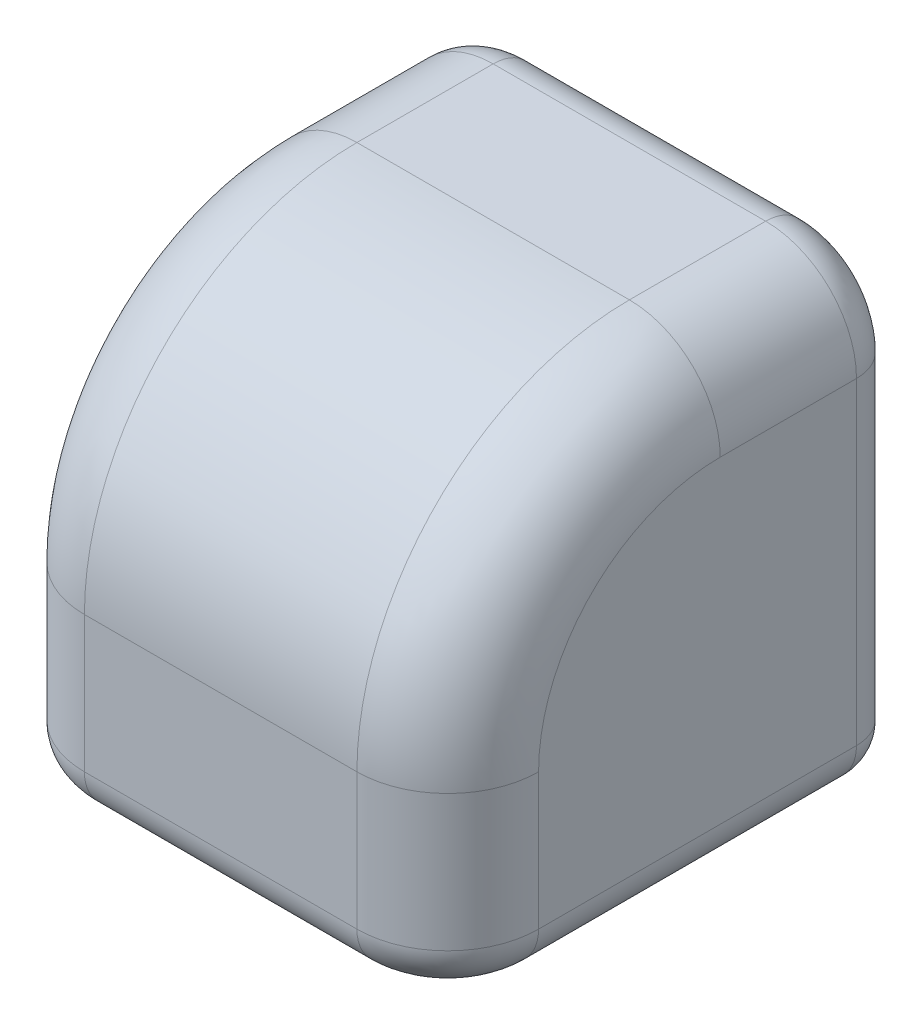
SolidWorks part; units mm, degrees
ref_plane "Front Plane" through (0, 0, 0) normal (0, 0, 1) x (1, 0, 0)
ref_plane "Top Plane" through (0, 0, 0) normal (0, 1, 0) x (1, 0, 0)
ref_plane "Right Plane" through (0, 0, 0) normal (1, 0, 0) x (0, 0, -1)
sketch "Sketch1" plane through (0, 0, 0) normal (0, 1, 0) x (1, 0, 0)
  line L1 (-25, 25) -> (25, 25)
  line L2 (-25, 25) -> (-25, -25)
  line L3 (-25, -25) -> (25, -25)
  line L4 (25, 25) -> (25, -25)
  line L5 (-25, 25) -> (25, -25) construction
  line L6 (-25, -25) -> (25, 25) construction
  point P0 (0, 0)
  dimension "D1" = 50
  dimension "D2" = 50
extrude "Boss-Extrude1" add sketch "Sketch1" along normal blind 50
sketch "Sketch2" plane through (0, 0, -25) normal (0, 0, -1) x (-1, 0, 0)
  line L0 (-25, 50) -> (-25, 0) construction
  line L1 (-25, 0) -> (25, 0) construction
  circle A0 centre (0, 25) radius 20
  dimension "D1" = 40
  dimension "D2" = 25
  dimension "D3" = 25
extrude "Cut-Extrude1" cut sketch "Sketch2" against normal blind 5
sketch "Sketch3" plane through (0, 0, 0) normal (0, -1, 0) x (1, 0, 0)
  circle A0 centre (0, 0) radius 20
  dimension "D1" = 40
extrude "Cut-Extrude5" cut sketch "Sketch3" against normal blind 2
fillet "Fillet10" radius 30 1 edges at (0, 50, 25)
fillet "Fillet11" radius 10 3 edges at (25, 10, 25) (25, 41.2132, 16.2132) (25, 50, -15)
fillet "Fillet12" radius 10 3 edges at (-25, 10, 25) (-25, 41.2132, 16.2132) (-25, 50, -15)
fillet "Fillet15" radius 5 5 edges at (25, 0, -5) (22.0711, 0, 22.0711) (0, 0, 25) (-22.0711, 0, 22.0711) (-25, 0, -5)
fillet "Fillet16" radius 5 8 edges at (23.5355, 1.4645, -25) (25, 22.5, -25) (22.0711, 47.0711, -25) (0, 50, -25) (-22.0711, 47.0711, -25) (-25, 22.5, -25) (-23.5355, 1.4645, -25) (0, 0, -25)
